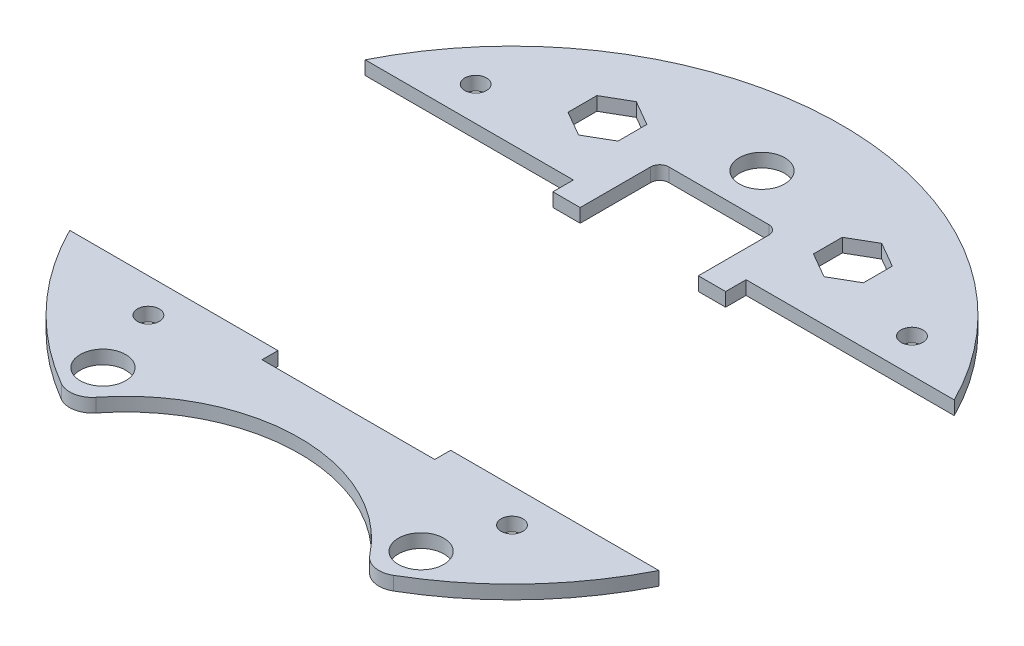
SolidWorks part; units mm, degrees
material "Acrylic (Medium-high impact)"
ref_plane "Front Plane" through (0, 0, 0) normal (0, 0, 1) x (1, 0, 0)
ref_plane "Top Plane" through (0, 0, 0) normal (0, 1, 0) x (1, 0, 0)
ref_plane "Right Plane" through (0, 0, 0) normal (1, 0, 0) x (0, 0, -1)
sketch "Sketch1" plane through (0, 0, 0) normal (0, 1, 0) x (1, 0, 0)
  line L0 (0, -85) -> (-32.4891, -64.8129) construction
  line L1 (0, -85) -> (0, 0) construction
  arc A0 (36.5434, -62.6165) -> (-36.5434, -62.6165) centre (0, 0) ccw
  arc A1 (30.0898, -61.3851) -> (-30.0898, -61.3851) centre (0, -85) ccw
  arc A2 (36.5434, -62.6165) -> (30.0898, -61.3851) centre (34.0231, -58.2982) cw
  arc A3 (-30.0898, -61.3851) -> (-36.5434, -62.6165) centre (-34.0231, -58.2982) cw
  dimension "D1" = 145
  dimension "D2" = 76.5
  dimension "D4" = 5
  dimension "D3" = 85
extrude "Boss-Extrude1" add sketch "Sketch1" along normal blind 3
sketch "solenoid placement" plane through (0, 3, 0) normal (0, 1, 0) x (1, 0, 0)
  line L4 (-19, -36) -> (19, -36)
  line L5 (-19, 28) -> (-19, -36)
  line L6 (19, 28) -> (-19, 28)
  line L7 (19, -36) -> (19, 28)
  line L8 (-19, -36) -> (19, -36)
  line L9 (-19, 28) -> (-19, -36)
  line L10 (19, 28) -> (-19, 28)
  line L11 (19, -36) -> (19, 28)
  dimension "D1" = 0
extrude "Cut-Extrude1" cut sketch "solenoid placement" against normal through all
sketch "Sketch5" plane through (0, 3, 0) normal (0, 1, 0) x (1, 0, 0)
  line L12 (-21.5, 51.1754) -> (-27, 54.3509)
  line L13 (-27, 54.3509) -> (-32.5, 51.1754)
  line L14 (-32.5, 51.1754) -> (-32.5, 44.8246)
  line L15 (-32.5, 44.8246) -> (-27, 41.6491)
  line L16 (-27, 41.6491) -> (-21.5, 44.8246)
  line L17 (-21.5, 44.8246) -> (-21.5, 51.1754)
  line L18 (-21.5, 51.1754) -> (-27, 54.3509)
  line L19 (-27, 54.3509) -> (-32.5, 51.1754)
  line L20 (-32.5, 51.1754) -> (-32.5, 44.8246)
  line L21 (-32.5, 44.8246) -> (-27, 41.6491)
  line L22 (-27, 41.6491) -> (-21.5, 44.8246)
  line L23 (-21.5, 44.8246) -> (-21.5, 51.1754)
  line L24 (21.5, 51.1754) -> (21.5, 44.8246)
  line L25 (21.5, 44.8246) -> (27, 41.6491)
  line L26 (27, 41.6491) -> (32.5, 44.8246)
  line L27 (32.5, 44.8246) -> (32.5, 51.1754)
  line L28 (32.5, 51.1754) -> (27, 54.3509)
  line L29 (27, 54.3509) -> (21.5, 51.1754)
  line L30 (21.5, 51.1754) -> (21.5, 44.8246)
  line L31 (21.5, 44.8246) -> (27, 41.6491)
  line L32 (27, 41.6491) -> (32.5, 44.8246)
  line L33 (32.5, 44.8246) -> (32.5, 51.1754)
  line L34 (32.5, 51.1754) -> (27, 54.3509)
  line L35 (27, 54.3509) -> (21.5, 51.1754)
  dimension "D1" = 0
  dimension "D2" = 0
extrude "Cut-Extrude5" cut sketch "Sketch5" against normal through all
sketch "Sketch6" plane through (0, 3, 0) normal (0, 1, 0) x (1, 0, 0)
  circle A1 centre (40, -40) radius 2.4
  circle A2 centre (40, -40) radius 2.4
  circle A3 centre (-40, -40) radius 2.4
  circle A4 centre (-40, -40) radius 2.4
  circle A5 centre (48, 40) radius 2.4
  circle A6 centre (48, 40) radius 2.4
  circle A7 centre (-48, 40) radius 2.4
  circle A8 centre (-48, 40) radius 2.4
  dimension "D1" = 0
  dimension "D2" = 0
  dimension "D3" = 0
  dimension "D4" = 0
extrude "Cut-Extrude6" cut sketch "Sketch6" against normal through all
sketch "Sketch3" plane through (0, 3, 0) normal (0, 1, 0) x (1, 0, 0)
  line L0 (-19, 28) -> (-19, 32.5)
  line L1 (72.5, -32.5) -> (-72.5, -32.5)
  line L2 (72.5, -32.5) -> (72.5, 32.5)
  line L3 (72.5, 32.5) -> (19, 32.5)
  line L4 (-72.5, -32.5) -> (-72.5, 32.5)
  line L5 (72.5, -32.5) -> (-72.5, 32.5) construction
  line L6 (72.5, 32.5) -> (-72.5, -32.5) construction
  line L7 (-19, 28) -> (19, 28)
  line L8 (19, 28) -> (19, 32.5)
  line L9 (-19, 32.5) -> (-72.5, 32.5)
  arc A0 (36.5434, -62.6165) -> (-36.5434, -62.6165) centre (0, 0) ccw construction
  point P0 (0, 0)
  dimension "D1" = 65
extrude "Cut-Extrude3" cut sketch "Sketch3" against normal through all
sketch "Sketch7" plane through (0, 3, 0) normal (0, 1, 0) x (1, 0, 0)
  line L8 (13, 28) -> (13, 43.5)
  line L9 (-13, 28) -> (13, 28)
  line L10 (-13, 43.5) -> (-13, 28)
  line L11 (11, 45.5) -> (-11, 45.5)
  line L20 (13, 28) -> (13, 43.5)
  line L21 (-13, 28) -> (13, 28)
  line L22 (-13, 43.5) -> (-13, 28)
  line L23 (11, 45.5) -> (-11, 45.5)
  arc A4 (-11, 45.5) -> (-13, 43.5) centre (-11, 43.5) ccw
  arc A5 (13, 43.5) -> (11, 45.5) centre (11, 43.5) ccw
  arc A10 (-11, 45.5) -> (-13, 43.5) centre (-11, 43.5) ccw
  arc A11 (13, 43.5) -> (11, 45.5) centre (11, 43.5) ccw
  dimension "D1" = 0
extrude "Cut-Extrude7" cut sketch "Sketch7" against normal through all
sketch "Sketch8" plane through (0, 3, 0) normal (0, -1, 0) x (1, 0, 0)
  circle A1 centre (35, 55) radius 5
  circle A2 centre (35, 55) radius 5
  circle A3 centre (-35, 55) radius 5
  circle A4 centre (-35, 55) radius 5
  dimension "D1" = 0
  dimension "D2" = 0
extrude "Cut-Extrude9" cut sketch "Sketch8" along normal through all
sketch "Sketch9" plane through (0, 3, 0) normal (0, -1, 0) x (1, 0, 0)
  circle A1 centre (0, -55) radius 5
  circle A2 centre (0, -55) radius 5
  dimension "D1" = 0
extrude "Cut-Extrude11" cut sketch "Sketch9" along normal through all
equation "\"smallPulleyTeeth\"= 30"
equation "\"largePulleyTeeth\"= 30"
equation "\"eighthThick\"= 3.0mm"
equation "\"sixteenthThick\"= 1.7mm"
equation "\"quarterThick\"=6.0mm"
equation "\"OD\"= 145mm"
equation "\"puckAngle\"= 60.5deg"
equation "\"D1@Sketch1\"=\"OD\""
equation "\"puckDiam\"= 76.5mm"
equation "\"D2@Sketch1\"=\"puckDiam\""
equation "\"D1@Boss-Extrude1\"=\"eighthThick\""
equation "\"axlePress\"= 5.9mm"
equation "\"press\"= 0.2mm"
equation "\"wheelClear\"= 0.3mm"
equation "\"10-32clear\"= 4.8mm"
equation "\"6-32clear\"= 3.3mm"
equation "\"8-32clear\"= 4.0mm"
equation "\"wheelHeight\"= 22mm"
equation "\"wheelWell\"= 65mm"
equation "\"D1@Sketch3\"=\"wheelWell\""
equation "\"puckDist\"= 85mm"
equation "\"scoopFillet\"= 5mm"
equation "\"4-40clear\"= 3.0mm"
equation "\"D3@Sketch1\"=\"puckDist\""
equation "\"D4@Sketch1\"=\"scoopFillet\""
